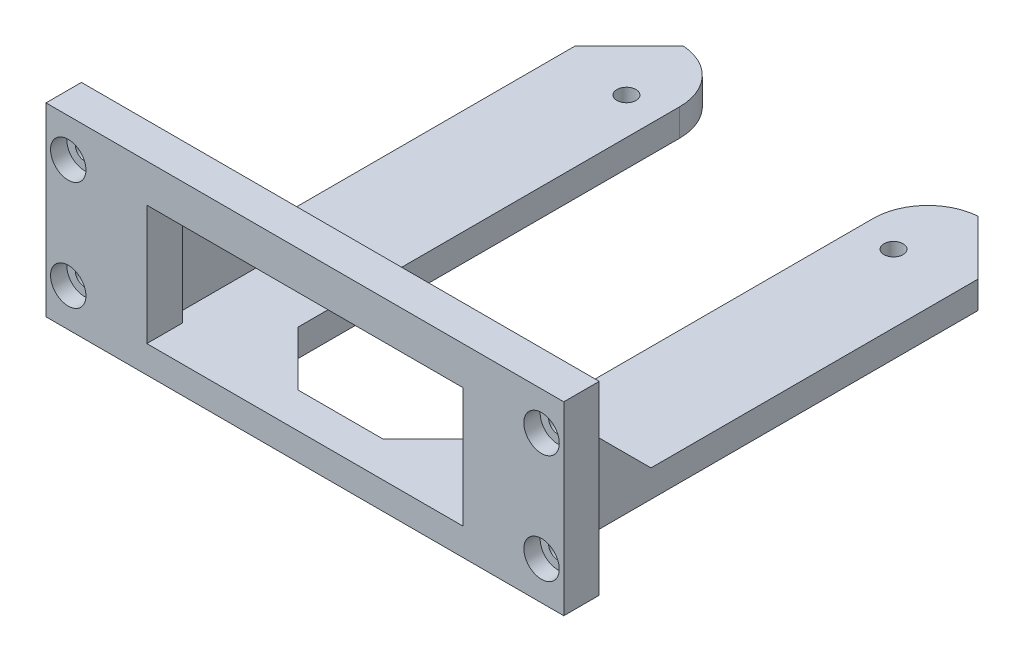
SolidWorks part; units mm, degrees
ref_plane "Front Plane" through (0, 0, 0) normal (0, 0, 1) x (1, 0, 0)
ref_plane "Top Plane" through (0, 0, 0) normal (0, 1, 0) x (1, 0, 0)
ref_plane "Right Plane" through (0, 0, 0) normal (1, 0, 0) x (0, 0, -1)
sketch "Sketch1" plane through (0, 0, 0) normal (0, 0, 1) x (1, 0, 0)
  line L1 (-47.5, 17) -> (47.5, 17)
  line L2 (-47.5, 17) -> (-47.5, -17)
  line L3 (-47.5, -17) -> (47.5, -17)
  line L4 (47.5, 17) -> (47.5, -17)
  line L5 (-47.5, 17) -> (47.5, -17) construction
  line L6 (-47.5, -17) -> (47.5, 17) construction
  point P0 (0, 0)
  dimension "D1" = 95
  dimension "D2" = 34
extrude "Boss-Extrude1" add sketch "Sketch1" along normal blind 6.5
sketch "Sketch2" plane through (0, 0, 0) normal (0, 0, -1) x (-1, 0, 0)
  line L0 (47.5, -17) -> (-47.5, -17) construction
  line L1 (-37, -17) -> (37, -17)
  line L2 (-37, -17) -> (-37, -12)
  line L3 (-37, -12) -> (37, -12)
  line L4 (37, -17) -> (37, -12)
  point P6 (0, -12)
  dimension "D1" = 74
  dimension "D2" = 5
extrude "Boss-Extrude2" add sketch "Sketch2" along normal blind 90
sketch "Sketch3" plane through (0, 0, 0) normal (0, 0, -1) x (-1, 0, 0)
  line L0 (37, -12) -> (-37, -12) construction
  line L1 (-29, -12) -> (29, -12)
  line L2 (-29, -12) -> (-29, 10)
  line L3 (-29, 10) -> (29, 10)
  line L4 (29, -12) -> (29, 10)
  point P6 (0, 10)
  dimension "D1" = 58
  dimension "D2" = 22
extrude "Cut-Extrude1" cut sketch "Sketch3" against normal blind 90
sketch "Sketch6" plane through (0, 0, 6.5) normal (0, 0, 1) x (1, 0, 0)
  point P0 (-43.42, 10)
  point P2 (-43.42, -10)
  point P4 (43.42, 10)
  point P6 (43.42, -10)
  dimension "D1" = 20
  dimension "D2" = 43.42
  dimension "D3" = 43.42
  dimension "D4" = 10
hole_wizard "CBORE for M3 SHCS1" positions "Sketch6" profile "Sketch5" counterbore size "M3" standard "ANSI Metric"
sketch "Sketch5" plane through (-43.42, 10, 6.5) normal (1, 0, 0) x (0, -1, 0)
  line L0 (0, 0) -> (0, 11.1215)
  line L1 (0, 11.1215) -> (1.7, 10.1)
  line L2 (1.7, 10.1) -> (1.7, 3)
  line L3 (1.7, 3) -> (3.25, 3)
  line L4 (3.25, 3) -> (3.25, 0)
  line L5 (3.25, 0) -> (0, 0)
  line L10 (0, 11.1215) -> (-1.7, 10.1) construction
  line L11 (0, -6.35) -> (0, 107.95) construction
  dimension "Hole Dia." = 3.4
  dimension "Hole Depth" = 10.1
  dimension "C'Bore Dia." = 6.5
  dimension "C'Bore Depth" = 3
  dimension "Drill Angle" = 118
sketch "Sketch7" plane through (0, 0, 0) normal (0, 0, -1) x (-1, 0, 0)
  line L0 (-29, 10) -> (-29, -12) construction
  line L9 (-37, -12) -> (-31, -12)
  line L10 (-37, -12) -> (-37, 8)
  line L11 (-37, 8) -> (-31, 8)
  line L12 (-31, -12) -> (-31, 8)
  line L13 (0, 15.125) -> (0, -15.125) construction
  line L14 (37, 8) -> (31, 8)
  line L15 (31, -12) -> (31, 8)
  line L16 (37, -12) -> (31, -12)
  line L17 (37, -12) -> (37, 8)
  dimension "D1" = 2
  dimension "D2" = 20
extrude "Boss-Extrude3" add sketch "Sketch7" along normal blind 20
chamfer "Chamfer1" distance 20 angle 45 2 edges at (34, 8, -20) (-34, 8, -20)
sketch "Sketch10" plane through (0, -12, 0) normal (0, 1, 0) x (1, 0, 0)
  line L0 (-29, -6.5) -> (29, -6.5) construction
  line L1 (0, -15.125) -> (0, 15.125) construction
  point P0 (-24.5, 77)
  point P2 (24.5, 77)
  point P4 (-24.5, 19)
  point P6 (24.5, 19)
  dimension "D1" = 58
  dimension "D2" = 49
  dimension "D3" = 25.5
  dimension "D4" = 24.5
hole_wizard "Ø1.0 (3.5) Diameter Hole1" positions "Sketch10" profile "Sketch11" hole size "Ø1.0" standard "ANSI Metric"
sketch "Sketch11" plane through (-24.5, -12, -77) normal (1, 0, 0) x (0, 0, 1)
  line L0 (0, 0) -> (0, 11.1515)
  line L1 (0, 11.1515) -> (1.75, 10.1)
  line L2 (1.75, 10.1) -> (1.75, 0)
  line L5 (1.75, 0) -> (0, 0)
  line L10 (0, 11.1515) -> (-1.75, 10.1) construction
  line L11 (0, -6.35) -> (0, 107.95) construction
  dimension "Hole Dia." = 3.5
  dimension "Hole Depth" = 10.1
  dimension "Drill Angle" = 118
sketch "Sketch12" plane through (0, -12, 0) normal (0, 1, 0) x (1, 0, 0)
  line L0 (-37, 90) -> (37, 90) construction
  line L1 (-17.75, 90) -> (17.75, 90)
  line L2 (-17.75, 90) -> (-17.75, 0)
  line L3 (-17.75, 0) -> (17.75, 0)
  line L4 (17.75, 90) -> (17.75, 0)
  line L5 (47.5, 0) -> (-47.5, 0) construction
  circle A1 centre (-24.5, 77) radius 1.75 construction
  circle A2 centre (24.5, 77) radius 1.75 construction
  dimension "D1" = 5
  dimension "D2" = 5
extrude "Cut-Extrude2" cut sketch "Sketch12" against normal blind 20
chamfer "Chamfer2" distance 10 angle 45 4 edges at (-17.75, -14.5, 0) (17.75, -14.5, 0) (37, -14.5, -90) (-37, -14.5, -90)
fillet "Fillet1" radius 10 2 edges at (-17.75, -14.5, -90) (17.75, -14.5, -90)
